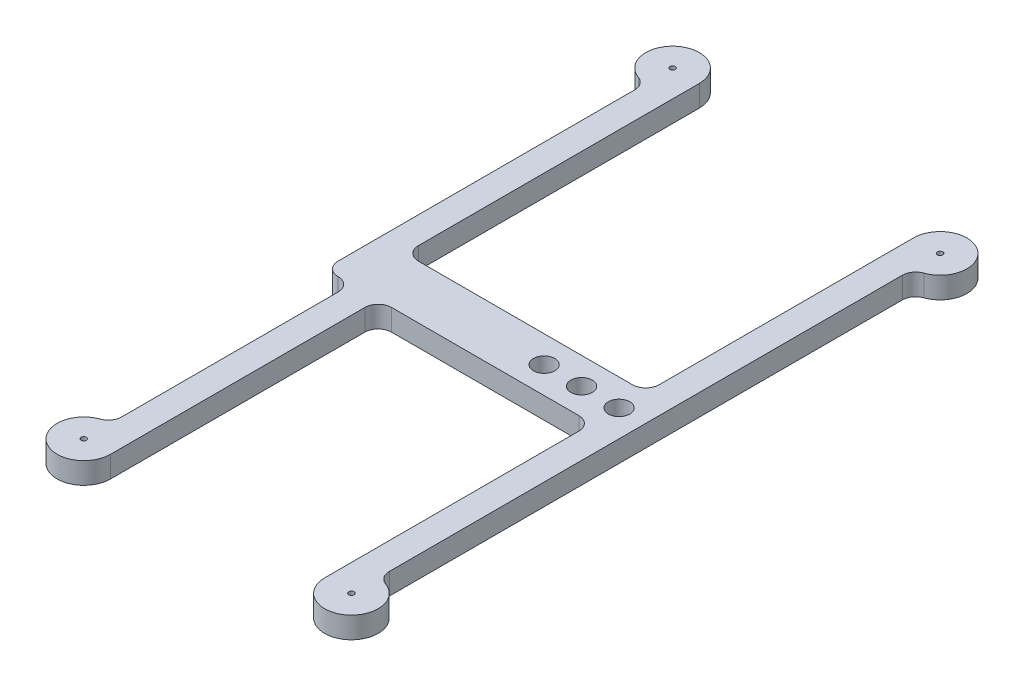
SolidWorks part; units mm, degrees
ref_plane "Front Plane" through (0, 0, 0) normal (0, 0, 1) x (1, 0, 0)
ref_plane "Top Plane" through (0, 0, 0) normal (0, 1, 0) x (1, 0, 0)
ref_plane "Right Plane" through (0, 0, 0) normal (1, 0, 0) x (0, 0, -1)
sketch "Sketch1" plane through (0, 0, 0) normal (0, 1, 0) x (1, 0, 0)
  line L0 (0, 0) -> (50, 0) construction
  line L1 (50, 0) -> (50, 110) construction
  line L2 (50, 110) -> (-5, 115) construction
  line L3 (-5, 115) -> (0, 0) construction
  line L4 (0, 50) -> (-5, 50)
  line L5 (45, 50) -> (5, 50)
  line L6 (50, 50) -> (50, 60)
  line L7 (45, 60) -> (0, 60)
  line L8 (-5, 50) -> (-5, 60)
  line L9 (50, 55) -> (-5, 55) construction
  line L10 (0, 5) -> (0, 50)
  line L12 (5, 0) -> (5, 50)
  line L14 (-5, 110) -> (-5, 60)
  line L16 (0, 115) -> (0, 60)
  line L18 (50, 105) -> (50, 60)
  line L20 (45, 110) -> (45, 60)
  line L22 (50, 5) -> (50, 50)
  line L24 (45, 0) -> (45, 50)
  arc A0 (-0.0205, 114.5473) -> (-5, 110) centre (-5, 115) ccw
  arc A1 (50, 105) -> (45, 110) centre (50, 110) ccw
  arc A2 (45, 0) -> (50, 5) centre (50, 0) ccw
  arc A3 (0, 5) -> (5, 0) centre (0, 0) ccw
  circle A4 centre (45, 55) radius 2
  circle A5 centre (38, 55) radius 2
  circle A6 centre (31, 55) radius 2
  circle A7 centre (-5, 115) radius 0.5
  circle A8 centre (50, 110) radius 0.5
  circle A9 centre (0, 0) radius 0.5
  circle A10 centre (50, 0) radius 0.5
  dimension "D5" = 10
  dimension "D6" = 10
  dimension "D7" = 10
  dimension "D8" = 10
  dimension "D17" = 4
  dimension "D20" = 4
  dimension "D21" = 4
  dimension "D22" = 1
  dimension "D23" = 1
  dimension "D24" = 1
  dimension "D25" = 1
  dimension "D1" = 50
  dimension "D2" = 110
  dimension "D3" = 5
  dimension "D4" = 5
  dimension "D9" = 10
  dimension "D10" = 50
  dimension "D11" = 10
  dimension "D12" = 5
  dimension "D13" = 5
  dimension "D14" = 5
  dimension "D15" = 5
  dimension "D16" = 5
  dimension "D18" = 7
  dimension "D19" = 7
  dimension "D26" = 5
extrude "Boss-Extrude1" add sketch "Sketch1" along normal blind 4 contours L10 A3 L12 L5 L24 A2 L22 L6 L18 A1 L20 L7 L16 A0 L14 L8 L4 A10 A9 A8 A7 A6 A5 A4 region at (22.6872, 0, -55.9764)
fillet "Fillet1" radius 2.5 10 edges at (50, 2, -105) (-5, 2, -110) (50, 2, -5) (0, 2, -5) (45, 2, -50) (45, 2, -60) (0, 2, -60) (5, 2, -50) (0, 2, -50) (-5, 2, -50)
